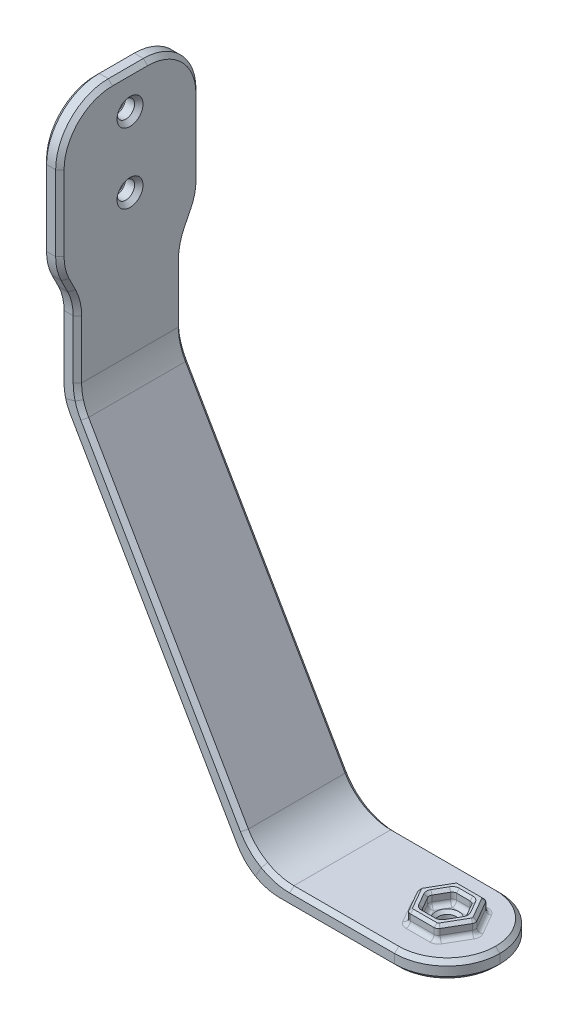
SolidWorks part; units mm, degrees
ref_plane "Front Plane" through (0, 0, 0) normal (0, 0, 1) x (1, 0, 0)
ref_plane "Top Plane" through (0, 0, 0) normal (0, 1, 0) x (1, 0, 0)
ref_plane "Right Plane" through (0, 0, 0) normal (1, 0, 0) x (0, 0, -1)
sketch "Sketch1" plane through (0, 0, 0) normal (0, 0, 1) x (1, 0, 0)
  line L0 (0, 0) -> (0, -47.5145)
  line L1 (0, -47.5145) -> (33.6108, -105.7302)
  line L2 (33.6108, -105.7302) -> (68.5358, -105.7302)
  dimension "D1" = 47.5145
  dimension "D3" = 150
  dimension "D4" = 120
  dimension "D5" = 34.925
  dimension "D2" = 58.2157
sketch "Sketch2" plane through (0, 0, 0) normal (0, 1, 0) x (1, 0, 0)
  line L1 (-1.5875, -9.525) -> (1.5875, -9.525)
  line L2 (-1.5875, -9.525) -> (-1.5875, 9.525)
  line L3 (-1.5875, 9.525) -> (1.5875, 9.525)
  line L4 (1.5875, -9.525) -> (1.5875, 9.525)
  line L5 (-1.5875, -9.525) -> (1.5875, 9.525) construction
  line L6 (-1.5875, 9.525) -> (1.5875, -9.525) construction
  point P0 (0, 0)
  dimension "D1" = 3.175
  dimension "D2" = 19.05
sweep "Sweep1" add profiles "Sketch2" path "Sketch1"
sketch "Sketch7" plane through (0, 0, 0) normal (1, 0, 0) x (0, 0, -1)
  line L0 (-12.7, -25.4) -> (-9.525, -31.75)
  line L1 (-12.7, 0) -> (12.7, 0)
  line L2 (-12.7, 0) -> (-12.7, -25.4)
  line L3 (-12.7, -25.4) -> (12.7, -25.4) construction
  line L4 (12.7, 0) -> (12.7, -25.4)
  line L5 (-9.525, 0) -> (-9.525, -47.0892) construction
  line L6 (-9.525, -31.75) -> (9.525, -31.75)
  line L7 (9.525, 0) -> (9.525, -47.0892) construction
  line L8 (9.525, -31.75) -> (12.7, -25.4)
  dimension "D1" = 25.4
  dimension "D2" = 25.4
  dimension "D3" = 6.35
extrude "Boss-Extrude1" add sketch "Sketch7" along normal mid plane 3.175 contours L2 L0 L6 L8 L4 L1
sketch "Sketch8" plane through (0, 0, 0) normal (1, 0, 0) x (0, 0, -1)
  line L0 (0, -19.05) -> (0, -6.35) construction
  line L1 (0, -6.35) -> (0, 0) construction
  circle A0 centre (0, -6.35) radius 1.5875
  circle A1 centre (0, -19.05) radius 1.5875
  dimension "D1" = 3.175
  dimension "D2" = 6.35
  dimension "D3" = 12.7
extrude "Cut-Extrude1" cut sketch "Sketch8" against normal through all both and the other way through all
sketch "Sketch9" plane through (0, -104.1427, 0) normal (0, 1, 0) x (1, 0, 0)
  line L0 (68.5358, 0) -> (59.0108, 0) construction
  line L1 (68.5358, -9.525) -> (68.5358, 9.525) construction
  circle A0 centre (59.0108, 0) radius 1.5875
  dimension "D1" = 3.175
  dimension "D2" = 9.525
extrude "Cut-Extrude2" cut sketch "Sketch9" against normal through all both and the other way through all
sketch "Sketch10" plane through (0, -104.1427, 0) normal (0, 1, 0) x (1, 0, 0)
  line L1 (60.6973, 2.921) -> (57.3244, 2.921)
  line L2 (57.3244, 2.921) -> (55.6379, 0)
  line L3 (55.6379, 0) -> (57.3244, -2.921)
  line L4 (57.3244, -2.921) -> (60.6973, -2.921)
  line L5 (60.6973, -2.921) -> (62.3837, 0)
  line L6 (62.3837, 0) -> (60.6973, 2.921)
  line L7 (61.6138, 4.5085) -> (56.4078, 4.5085)
  line L8 (56.4078, 4.5085) -> (53.8049, 0)
  line L9 (53.8049, 0) -> (56.4078, -4.5085)
  line L10 (56.4078, -4.5085) -> (61.6138, -4.5085)
  line L11 (61.6138, -4.5085) -> (64.2168, 0)
  line L12 (64.2168, 0) -> (61.6138, 4.5085)
  circle A0 centre (59.0108, 0) radius 2.921 construction
  circle A1 centre (59.0108, 0) radius 4.5085 construction
  dimension "D1" = 5.842
  dimension "D2" = 1.5875
extrude "Boss-Extrude2" add sketch "Sketch10" along normal blind 2.3813
fillet "Fillet1" radius 9.525 12 edges at (0, -31.75, -9.525) (0, -25.4, -12.7) (0, -31.75, 9.525) (0, -25.4, 12.7) (0, 0, -12.7) (0, 0, 12.7) (68.5358, -105.7302, -9.525) (68.5358, -105.7302, 9.525) (1.5875, -47.0892, 0) (-1.5875, -47.9399, 0) (32.6943, -107.3177, 0) (34.5274, -104.1427, 0)
fillet "Fillet2" radius 0.7937 24 edges at (64.2168, -102.9521, 0) (61.6138, -102.9521, 4.5085) (53.8049, -102.9521, 0) (56.4078, -102.9521, -4.5085) (61.6138, -102.9521, -4.5085) (56.4078, -102.9521, 4.5085) (55.6379, -102.9521, 0) (57.3244, -102.9521, 2.921) (60.6973, -102.9521, 2.921) (62.3837, -102.9521, 0) (60.6973, -102.9521, -2.921) (57.3244, -102.9521, -2.921) (59.0108, -104.1427, 2.921) (56.4812, -104.1427, 1.4605) (56.4812, -104.1427, -1.4605) (61.5405, -104.1427, -1.4605) (61.5405, -104.1427, 1.4605) (59.0108, -104.1427, -2.921) (59.0108, -104.1427, -4.5085) (55.1064, -104.1427, -2.2543) (55.1064, -104.1427, 2.2543) (59.0108, -104.1427, 4.5085) (62.9153, -104.1427, -2.2543) (62.9153, -104.1427, 2.2542)
chamfer "Chamfer1" distance 0.762 angle 45 58 edges at (65.746, -107.3177, 6.7352) (65.746, -107.3177, -6.7352) (48.6022, -107.3177, 9.525) (48.6022, -107.3177, -9.525) (35.7283, -106.9931, 9.525) (35.7283, -106.9931, -9.525) (31.4584, -104.5279, 9.525) (31.4584, -104.5279, -9.525) (14.8166, -76.3527, 9.525) (14.8166, -76.3527, -9.525) (-0.8625, -49.0327, 9.525) (-0.8625, -49.0327, -9.525) (-1.506, -46.631, 9.525) (-1.506, -46.631, -9.525) (-1.5875, -39.6931, 9.525) (-1.5875, -31.8102, 9.7798) (-1.5875, -28.575, 11.1125) (-1.5875, -25.3398, 12.4452) (-1.5875, -16.3382, 12.7) (-1.5875, -2.7898, 9.9102) (-1.5875, 0, 0) (-1.5875, -2.7898, -9.9102) (-1.5875, -16.3382, -12.7) (-1.5875, -25.3398, -12.4452) (-1.5875, -28.575, -11.1125) (-1.5875, -31.8102, -9.7798) (-1.5875, -39.6931, -9.525) (-1.5875, -19.05, -1.5875) (-1.5875, -6.35, -1.5875) (65.746, -104.1427, -6.7352) (65.746, -104.1427, 6.7352) (49.5187, -104.1427, -9.525) (49.5187, -104.1427, 9.525) (37.5614, -103.8181, -9.525) (37.5614, -103.8181, 9.525) (33.2914, -101.3529, -9.525) (33.2914, -101.3529, 9.525) (17.3207, -74.3398, -9.525) (17.3207, -74.3398, 9.525) (2.3125, -48.182, -9.525) (2.3125, -48.182, 9.525) (1.669, -45.7802, -9.525) (1.669, -45.7802, 9.525) (1.5875, -39.2677, -9.525) (1.5875, -31.8102, -9.7798) (1.5875, -28.575, -11.1125) (1.5875, -25.3398, -12.4452) (1.5875, -16.3382, -12.7) (1.5875, -2.7898, -9.9102) (1.5875, 0, 0) (1.5875, -2.7898, 9.9102) (1.5875, -16.3382, 12.7) (1.5875, -25.3398, 12.4452) (1.5875, -28.575, 11.1125) (1.5875, -31.8102, 9.7798) (1.5875, -39.2677, 9.525) (1.5875, -20.6375, 0) (1.5875, -7.9375, 0)
chamfer "Chamfer2" distance 0.508 angle 45 26 edges at (60.5983, -104.1427, 0) (57.4233, -107.3177, 0) (57.3858, -101.7614, -2.8147) (56.4812, -101.7614, -1.4605) (55.7607, -101.7614, 0) (56.4812, -101.7614, 1.4605) (57.3858, -101.7614, 2.8147) (59.0108, -101.7614, 2.921) (60.6359, -101.7614, 2.8147) (61.5405, -101.7614, 1.4605) (62.2609, -101.7614, 0) (61.5405, -101.7614, -1.4605) (60.6359, -101.7614, -2.8147) (59.0108, -101.7614, -2.921) (61.5524, -101.7614, 4.4022) (59.0108, -101.7614, 4.5085) (56.4692, -101.7614, 4.4022) (55.1064, -101.7614, 2.2543) (53.9277, -101.7614, 0) (55.1064, -101.7614, -2.2543) (56.4692, -101.7614, -4.4022) (59.0108, -101.7614, -4.5085) (61.5524, -101.7614, -4.4022) (62.9153, -101.7614, -2.2543) (64.094, -101.7614, 0) (62.9153, -101.7614, 2.2542)
equation "\"D2@Sketch1\"=2.59807621 - 0.3069935 + 0.0008725"
equation "\"D1@Sketch1\"=1.25+0.1875+0.433151"
